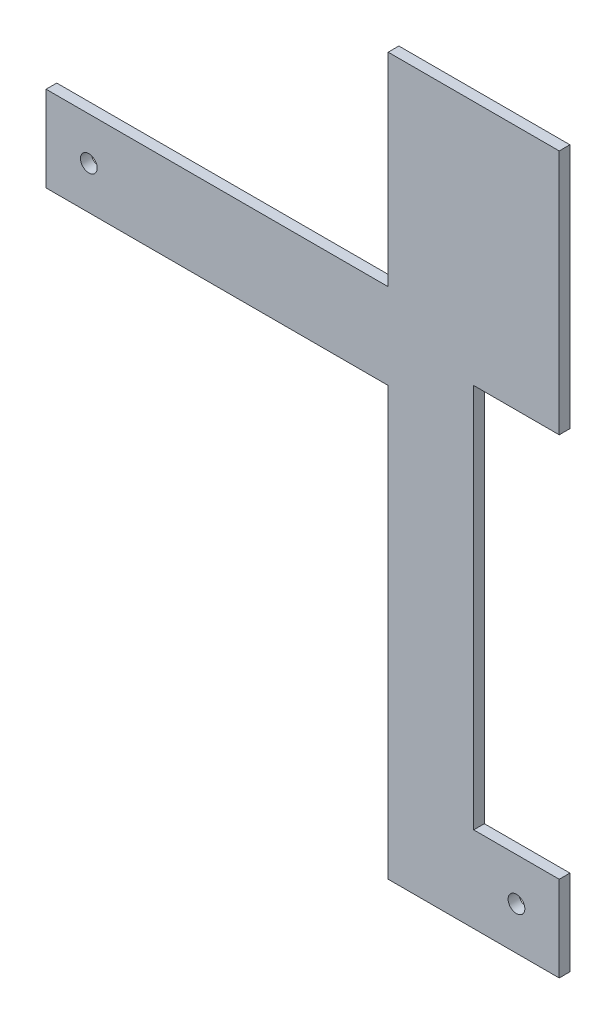
SolidWorks part; units mm, degrees
ref_plane "Front Plane" through (0, 0, 0) normal (1, 0, 0) x (0, 1, 0)
ref_plane "Top Plane" through (0, 0, 0) normal (0, 0, 1) x (0, 1, 0)
ref_plane "Right Plane" through (0, 0, 0) normal (0, 1, 0) x (-1, 0, 0)
sketch "Sketch1" plane through (0, 0, 0) normal (0, 0, 1) x (0, 1, 0)
  line L1 (-106.3625, -12.7) -> (106.3625, -12.7) construction
  line L2 (-106.3625, -12.7) -> (-106.3625, 12.7) construction
  line L3 (-106.3625, 12.7) -> (106.3625, 12.7) construction
  line L4 (106.3625, -12.7) -> (106.3625, 12.7) construction
  line L5 (-106.3625, -12.7) -> (106.3625, 12.7) construction
  line L6 (-106.3625, 12.7) -> (106.3625, -12.7) construction
  line L7 (-106.3625, -12.7) -> (-80.9625, -12.7) construction
  line L8 (-106.3625, -12.7) -> (-106.3625, -38.1) construction
  line L9 (-106.3625, -38.1) -> (-80.9625, -38.1) construction
  line L10 (-80.9625, -12.7) -> (-80.9625, -38.1) construction
  line L13 (-80.9625, -12.7) -> (-80.9625, -38.1)
  line L14 (-80.9625, -38.1) -> (-106.3625, -38.1)
  line L15 (-106.3625, -38.1) -> (-106.3625, 12.7)
  line L17 (20.6375, 12.7) -> (46.0375, 12.7) construction
  line L18 (20.6375, 12.7) -> (20.6375, 114.3) construction
  line L19 (20.6375, 114.3) -> (46.0375, 114.3) construction
  line L20 (46.0375, 12.7) -> (46.0375, 114.3) construction
  line L21 (46.0375, 12.7) -> (46.0375, 114.3)
  line L22 (46.0375, 114.3) -> (20.6375, 114.3)
  line L23 (20.6375, 114.3) -> (20.6375, 12.7)
  line L24 (20.6375, 12.7) -> (-106.3625, 12.7)
  line L25 (-80.9625, -12.7) -> (33.3375, -12.7)
  line L26 (33.3375, -12.7) -> (106.3625, -12.7) construction
  line L27 (33.3375, -12.7) -> (33.3375, -38.1) construction
  line L29 (106.3625, -12.7) -> (106.3625, -63.5) construction
  line L34 (33.3375, -12.7) -> (33.3375, -38.1)
  line L35 (33.3375, -38.1) -> (106.3625, -38.1)
  line L39 (106.3625, -38.1) -> (106.3625, 12.7)
  line L40 (106.3625, 12.7) -> (46.0375, 12.7)
  point P0 (0, 0)
  point P17 (33.3375, -25.4)
  dimension "D1" = 212.725
  dimension "D2" = 25.4
  dimension "D3" = 25.4
  dimension "D4" = 25.4
  dimension "D5" = 101.6
  dimension "D6" = 25.4
  dimension "D7" = 127
  dimension "D8" = 139.7
  dimension "D9" = 25.4
extrude "Boss-Extrude1" add sketch "Sketch1" along normal blind 3.175
sketch "Sketch2" plane through (0, 0, 3.175) normal (0, 0, 1) x (1, 0, 0)
  line L0 (38.1, -106.3625) -> (38.1, -80.9625) construction
  line L1 (-12.7, -106.3625) -> (38.1, -106.3625) construction
  line L2 (-114.3, 46.0375) -> (-114.3, 20.6375) construction
  line L3 (-114.3, 20.6375) -> (-12.7, 20.6375) construction
  point P0 (25.4, -93.6625)
  point P1 (-153.252, -35.1554)
  point P6 (-101.6, 33.3375)
  point P8 (-174.4616, 15.3753)
  dimension "D1" = 12.7
  dimension "D2" = 12.7
  dimension "D3" = 12.7
  dimension "D4" = 12.7
hole_wizard "#9 (0.196) Diameter Hole1" positions "Sketch2" profile "Sketch3" hole size "#9" standard "ANSI Inch" end condition through all
sketch "Sketch3" plane through (25.4, -93.6625, 3.175) normal (1, 0, 0) x (0, -1, 0)
  line L0 (0, 0) -> (0, 3.175)
  line L1 (0, 3.175) -> (2.4892, 3.175)
  line L2 (2.4892, 3.175) -> (2.4892, 0)
  line L5 (2.4892, 0) -> (0, 0)
  line L11 (0, -6.35) -> (0, 107.95) construction
  dimension "Thru Hole Dia." = 4.9784
  dimension "Thru Hole Depth" = 3.175
